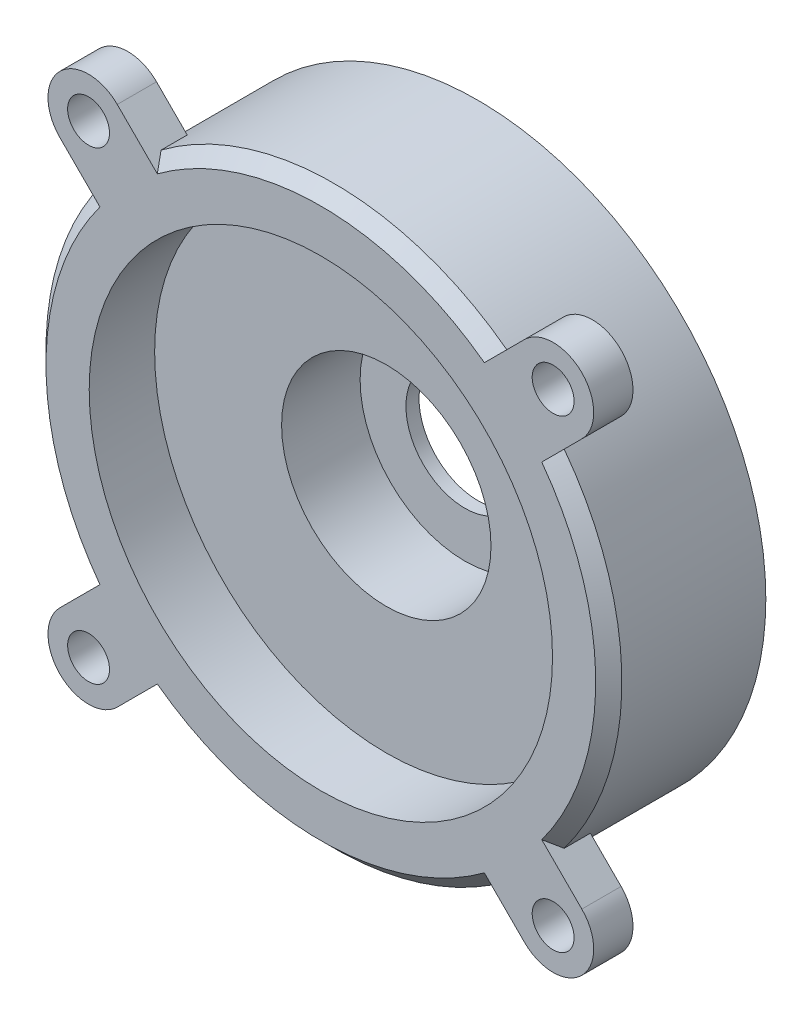
SolidWorks part; units mm, degrees
ref_plane "Front Plane" through (0, 0, 0) normal (0, 0, 1) x (1, 0, 0)
ref_plane "Top Plane" through (0, 0, 0) normal (0, 1, 0) x (1, 0, 0)
ref_plane "Right Plane" through (0, 0, 0) normal (1, 0, 0) x (0, 0, -1)
sketch "Sketch1" plane through (0, 0, 0) normal (0, 0, 1) x (1, 0, 0)
  circle A0 centre (0, 0) radius 22
  dimension "D1" = 44
extrude "Boss-Extrude1" add sketch "Sketch1" along normal mid plane 12
chamfer "Chamfer1" distance 1 angle 45 1 edges at (22, 0, 6)
sketch "Sketch8" plane through (0, 0, 6) normal (0, 0, 1) x (1, 0, 0)
  line L1 (15.5563, 19.9404) -> (12.4945, 16.8786)
  line L6 (19.9404, 15.5563) -> (16.8786, 12.4945)
  line L7 (12.4945, 16.8786) -> (16.8786, 12.4945)
  line L8 (19.9404, -15.5563) -> (16.8786, -12.4945)
  line L9 (15.5563, -19.9404) -> (12.4945, -16.8786)
  line L10 (16.8786, -12.4945) -> (12.4945, -16.8786)
  line L11 (-15.5563, -19.9404) -> (-12.4945, -16.8786)
  line L12 (-19.9404, -15.5563) -> (-16.8786, -12.4945)
  line L13 (-12.4945, -16.8786) -> (-16.8786, -12.4945)
  line L14 (-19.9404, 15.5563) -> (-16.8786, 12.4945)
  line L15 (-15.5563, 19.9404) -> (-12.4945, 16.8786)
  line L16 (-16.8786, 12.4945) -> (-12.4945, 16.8786)
  circle A2 centre (17.7484, 17.7484) radius 1.6
  circle A3 centre (17.7484, -17.7484) radius 1.6
  arc A4 (19.9404, 15.5563) -> (15.5563, 19.9404) centre (17.7484, 17.7484) ccw
  arc A5 (15.5563, -19.9404) -> (19.9404, -15.5563) centre (17.7484, -17.7484) ccw
  circle A6 centre (0, 0) radius 21 construction
  circle A7 centre (-17.7484, -17.7484) radius 1.6
  arc A8 (-19.9404, -15.5563) -> (-15.5563, -19.9404) centre (-17.7484, -17.7484) ccw
  circle A9 centre (-17.7484, 17.7484) radius 1.6
  arc A10 (-15.5563, 19.9404) -> (-19.9404, 15.5563) centre (-17.7484, 17.7484) ccw
  point P9 (0, 0)
  point P31 (0, 0)
  dimension "D1" = 4
extrude "Boss-Extrude2" add sketch "Sketch8" against normal blind 3
sketch "Sketch9" plane through (0, 0, 6) normal (0, 0, 1) x (1, 0, 0)
  circle A0 centre (0, 0) radius 17.7
extrude "Cut-Extrude1" cut sketch "Sketch9" against normal blind 5
sketch "Sketch10" plane through (0, 0, 1) normal (0, 0, 1) x (1, 0, 0)
  circle A0 centre (0, 0) radius 8
extrude "Cut-Extrude2" cut sketch "Sketch10" against normal blind 6
sketch "Sketch11" plane through (0, 0, -5) normal (0, 0, 1) x (1, 0, 0)
  circle A0 centre (0, 0) radius 4.5
extrude "Cut-Extrude3" cut sketch "Sketch11" against normal blind 1
